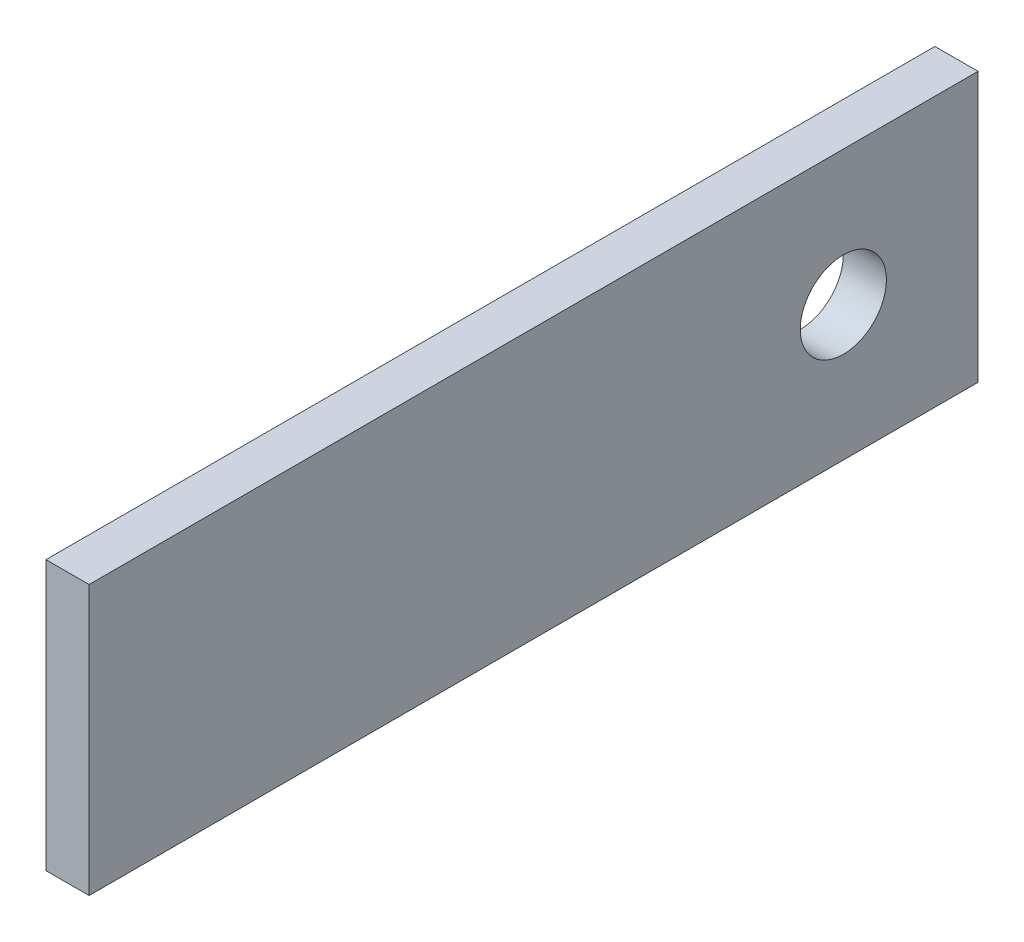
SolidWorks part; units mm, degrees
material "Perspex (TM) GS Acrylic Cast Sheet"
ref_plane "Front Plane" through (0, 0, 0) normal (0, 0, 1) x (1, 0, 0)
ref_plane "Top Plane" through (0, 0, 0) normal (0, 1, 0) x (1, 0, 0)
ref_plane "Right Plane" through (0, 0, 0) normal (1, 0, 0) x (0, 0, -1)
sketch "Sketch1" plane through (0, 0, 0) normal (1, 0, 0) x (0, 0, -1)
  line L0 (-70, 12.5) -> (-70, -12.5)
  line L2 (12.5, 12.5) -> (12.5, -12.5)
  line L19 (-70, 12.5) -> (12.5, 12.5)
  line L20 (-70, -12.5) -> (12.5, -12.5)
  circle A0 centre (0, 0) radius 4
  point P2 (0, 0)
  point P3 (12.5, 0)
  point P18 (0, 0)
  dimension "D1" = 8
  dimension "D2" = 25
  dimension "D5" = 70
  dimension "D6" = 12.5
extrude "Boss-Extrude1" add sketch "Sketch1" along normal blind 4
sketch "Sketch2" plane through (4, 0, 0) normal (1, 0, 0) x (0, 0, -1)
  line L0 (0, 0) -> (-70, 0) construction
  line L1 (-70, 12.5) -> (-70, -12.5) construction
